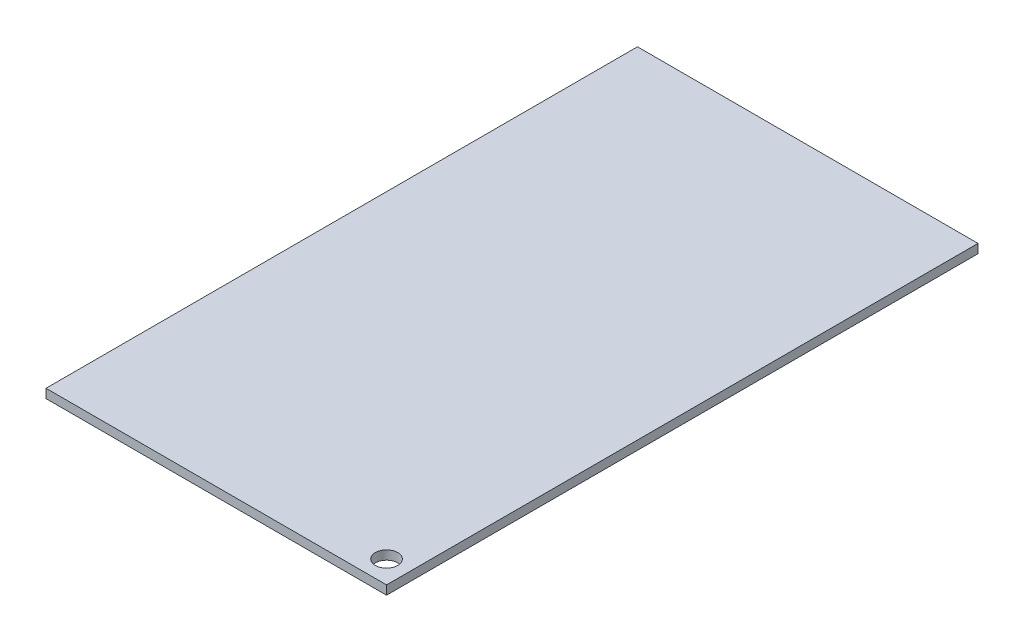
SolidWorks part; units mm, degrees
ref_plane "Front Plane" through (0, 0, 0) normal (0, 0, 1) x (1, 0, 0)
ref_plane "Top Plane" through (0, 0, 0) normal (0, 1, 0) x (1, 0, 0)
ref_plane "Right Plane" through (0, 0, 0) normal (1, 0, 0) x (0, 0, -1)
sketch "Sketch1" plane through (0, 0, 0) normal (0, 1, 0) x (1, 0, 0)
  line L1 (0, 0) -> (38, 0)
  line L2 (0, 0) -> (0, 66)
  line L3 (0, 66) -> (38, 66)
  line L4 (38, 0) -> (38, 66)
  dimension "D1" = 38
  dimension "D2" = 66
extrude "Boss-Extrude1" add sketch "Sketch1" along normal blind 1
sketch "Sketch2" plane through (0, 1, 0) normal (0, 1, 0) x (1, 0, 0)
  line L0 (0, 0) -> (38, 0) construction
  line L1 (38, 0) -> (38, 66) construction
  circle A0 centre (35.5, 2.5) radius 1.25
  dimension "D3" = 2.5
  dimension "D1" = 2.5
  dimension "D2" = 2.5
extrude "Cut-Extrude1" cut sketch "Sketch2" against normal through all
